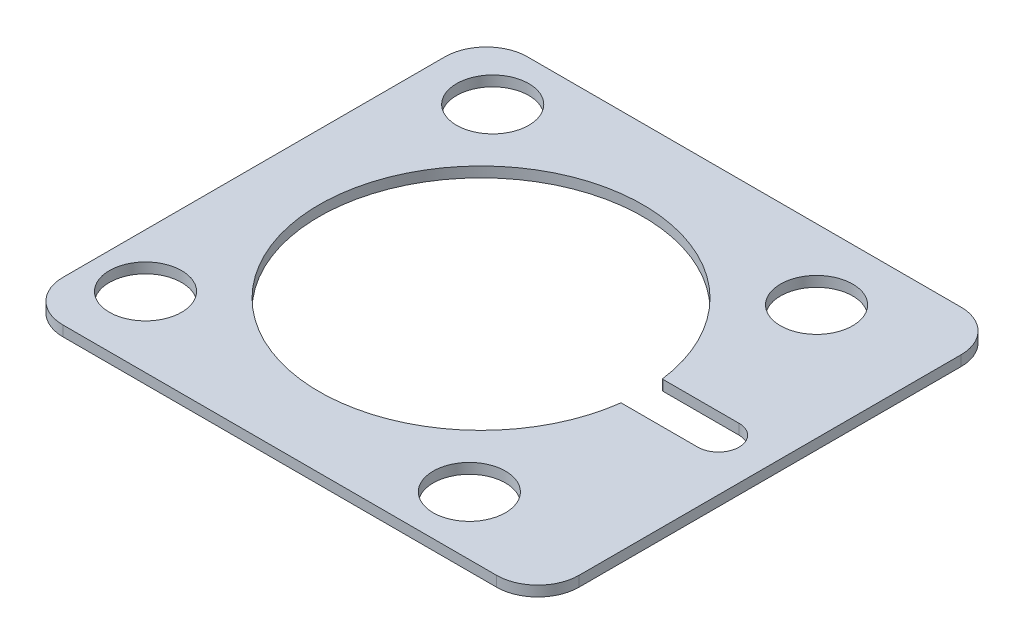
SolidWorks part; units mm, degrees
material "Rubber"
ref_plane "Front Plane" through (0, 0, 0) normal (0, 0, 1) x (1, 0, 0)
ref_plane "Top Plane" through (0, 0, 0) normal (0, 1, 0) x (1, 0, 0)
ref_plane "Right Plane" through (0, 0, 0) normal (1, 0, 0) x (0, 0, -1)
sketch "Sketch1" plane through (0, 0, 0) normal (0, 1, 0) x (1, 0, 0)
  line L0 (-18.8371, 0) -> (20.9258, 0) construction
  line L1 (-10.5, -11.25) -> (10.5, -11.25)
  line L2 (-12.5, -9.25) -> (-12.5, 9.25)
  line L3 (-10.5, 11.25) -> (10.5, 11.25)
  line L4 (12.5, -9.25) -> (12.5, 9.25)
  line L5 (-12.5, -11.25) -> (12.5, 11.25) construction
  line L6 (-12.5, 11.25) -> (12.5, -11.25) construction
  line L7 (-1.5, 13.6277) -> (-1.5, -14.894) construction
  line L8 (10, 0) -> (6.344, 0) construction
  line L9 (10, -1) -> (6.344, -1)
  line L10 (10, 1) -> (6.344, 1)
  arc A0 (10.5, 11.25) -> (12.5, 9.25) centre (10.5, 9.25) cw
  arc A1 (10.5, -11.25) -> (12.5, -9.25) centre (10.5, -9.25) ccw
  arc A2 (-10.5, -11.25) -> (-12.5, -9.25) centre (-10.5, -9.25) cw
  arc A3 (-12.5, 9.25) -> (-10.5, 11.25) centre (-10.5, 9.25) cw
  circle A4 centre (-1.5, 0) radius 11.5 construction
  circle A5 centre (-9.344, 8.4096) radius 1.75
  circle A6 centre (-9.9096, -7.844) radius 1.75
  circle A7 centre (6.344, -8.4096) radius 1.75
  circle A8 centre (6.9096, 7.844) radius 1.75
  arc A9 (10, -1) -> (10, 1) centre (10, 0) ccw
  arc A10 (6.344, 1) -> (6.2803, 0.998) centre (6.344, 0) ccw
  arc A11 (6.2803, 0.998) -> (6.2803, -0.998) centre (-1.5, 0) ccw
  arc A12 (6.2803, -0.998) -> (6.344, -1) centre (6.344, 0) ccw
  point P0 (0, 0)
  point P28 (8.172, 0)
  point P35 (-1.5, 0)
  dimension "D3" = 2
  dimension "D5" = 23
  dimension "D6" = 3.5
  dimension "D11" = 15.688
  dimension "D16" = 1
  dimension "D1" = 22.5
  dimension "D2" = 25
  dimension "D4" = 11
  dimension "D8" = 11.5
  dimension "D9" = 11.5
  dimension "D10" = 2
  dimension "D12" = 10.25
  dimension "D13" = 4.328
  dimension "D14" = 162.084
  dimension "D15" = 6.156
  dimension "D17" = 1.828
  dimension "D7" = 4
extrude "Boss-Extrude1" add sketch "Sketch1" along normal blind 0.5
